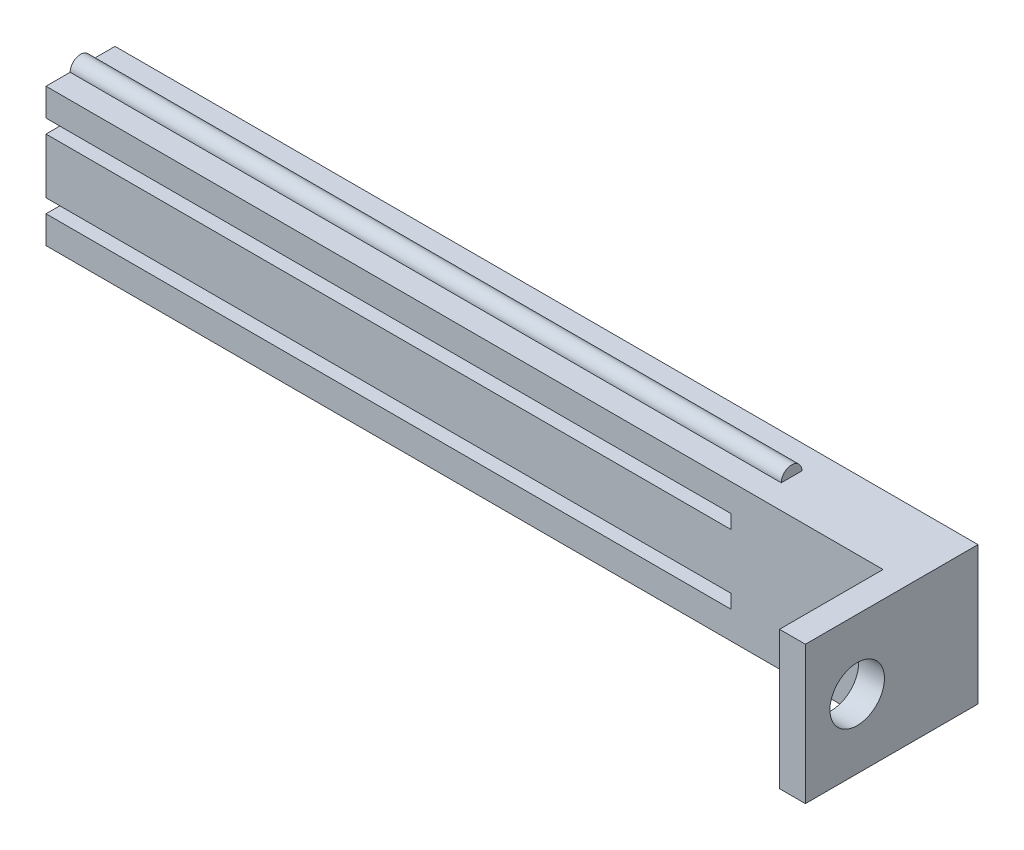
SolidWorks part; units mm, degrees
ref_plane "Front Plane" through (0, 0, 0) normal (0, 0, 1) x (1, 0, 0)
ref_plane "Top Plane" through (0, 0, 0) normal (0, 1, 0) x (1, 0, 0)
ref_plane "Right Plane" through (0, 0, 0) normal (1, 0, 0) x (0, 0, -1)
sketch "Sketch1" plane through (0, 0, 0) normal (0, 0, 1) x (1, 0, 0)
  line L1 (-147.2787, 68.6667) -> (102.7213, 68.6667)
  line L2 (-147.2787, 68.6667) -> (-147.2787, 28.6667)
  line L3 (-147.2787, 28.6667) -> (102.7213, 28.6667)
  line L4 (102.7213, 68.6667) -> (102.7213, 28.6667)
  dimension "D1" = 250
  dimension "D2" = 40
extrude "Boss-Extrude1" add sketch "Sketch1" along normal blind 20
sketch "Sketch2" plane through (0, 0, 20) normal (0, 0, 1) x (1, 0, 0)
  line L0 (-147.2787, 28.6667) -> (102.7213, 28.6667) construction
  line L1 (102.7213, 68.6667) -> (95.2213, 68.6667)
  line L2 (102.7213, 68.6667) -> (102.7213, 28.6667)
  line L3 (102.7213, 28.6667) -> (95.2213, 28.6667)
  line L4 (95.2213, 68.6667) -> (95.2213, 28.6667)
  dimension "D1" = 7.5
extrude "Boss-Extrude2" add sketch "Sketch2" along normal blind 30
sketch "Sketch4" plane through (-147.2787, 0, 0) normal (-1, 0, 0) x (0, 0, 1)
  line L0 (7, 68.6667) -> (13, 68.6667)
  line L1 (7, 28.6667) -> (13, 28.6667)
  arc A0 (13, 68.6667) -> (7, 68.6667) centre (10, 68.6667) ccw
  arc A1 (7, 28.6667) -> (13, 28.6667) centre (10, 28.6667) ccw
  dimension "D1" = 6
  dimension "D2" = 6
extrude "Boss-Extrude3" add sketch "Sketch4" against normal blind 206
sketch "Sketch6" plane through (-147.2787, 0, 0) normal (-1, 0, 0) x (0, 0, 1)
  line L0 (20, 68.6667) -> (20, 28.6667) construction
  line L1 (20, 60.6667) -> (15, 60.6667)
  line L2 (20, 60.6667) -> (20, 56.6667)
  line L3 (20, 56.6667) -> (15, 56.6667)
  line L6 (20, 68.6667) -> (13, 68.6667) construction
  line L7 (20, 40.6667) -> (15, 40.6667)
  line L8 (20, 40.6667) -> (20, 36.6667)
  line L9 (20, 36.6667) -> (15, 36.6667)
  line L11 (20, 28.6667) -> (13, 28.6667) construction
  line L12 (10, 63.6667) -> (10, 53.6667)
  line L13 (15, 56.6667) -> (15, 53.6667)
  line L14 (10, 63.6667) -> (15, 63.6667)
  line L15 (10, 63.6667) -> (10, 53.6667)
  line L16 (10, 53.6667) -> (15, 53.6667)
  line L17 (15, 63.6667) -> (15, 60.6667)
  line L18 (10, 43.6667) -> (15, 43.6667)
  line L19 (10, 43.6667) -> (10, 33.6667)
  line L20 (10, 33.6667) -> (15, 33.6667)
  line L21 (15, 43.6667) -> (15, 40.6667)
  line L22 (10, 43.6667) -> (10, 33.6667)
  line L24 (15, 36.6667) -> (15, 33.6667)
  point P27 (12.5, 63.6667)
  point P28 (12.5, 53.6667)
  line M24 (20, 28.6667) -> (20, 68.6667)
  dimension "D1" = 8
  dimension "D2" = 8
  dimension "D3" = 4
  dimension "D4" = 4
  dimension "D5" = 5
  dimension "D6" = 5
  dimension "D7" = 10
  dimension "D8" = 10
  dimension "D9" = 3
  dimension "D10" = 3
extrude "Cut-Extrude1" cut sketch "Sketch6" against normal blind 198.5 contours L17 L14 L12 L16 L13 L3 L1 M24 | L24 L9 L7 L21 L18 L19 L20 M24 region at (-147.2787, 58.6667, 13.9286) region at (-147.2787, 38.6667, 13.9286)
sketch "Sketch7" plane through (95.2213, 0, 0) normal (-1, 0, 0) x (0, 0, 1)
  circle A0 centre (35, 48.6667) radius 7.9
  point P6 (35, 48.6667)
  dimension "D1" = 15.8
extrude "Cut-Extrude2" cut sketch "Sketch7" against normal through all
